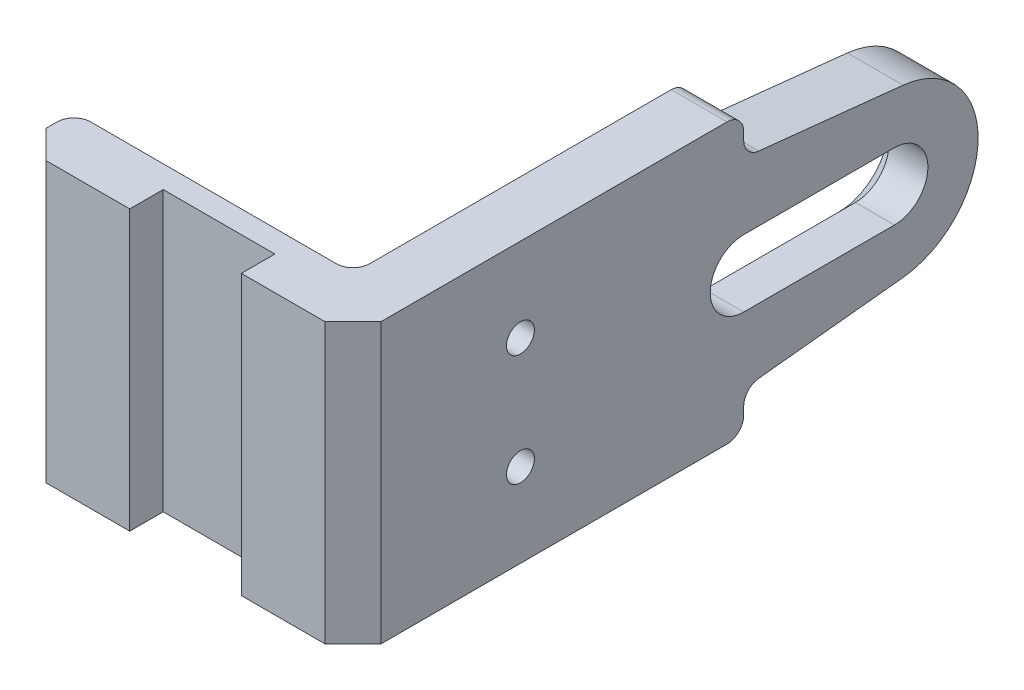
SolidWorks part; units mm, degrees
material "2014-T6"
ref_plane "Front Plane" through (0, 0, 0) normal (0, 0, 1) x (1, 0, 0)
ref_plane "Top Plane" through (0, 0, 0) normal (0, 1, 0) x (1, 0, 0)
ref_plane "Right Plane" through (0, 0, 0) normal (1, 0, 0) x (0, 0, -1)
sketch "Sketch1" plane through (0, 0, 0) normal (0, 1, 0) x (1, 0, 0)
  line L1 (0, 0) -> (-30, 0)
  line L2 (0, 0) -> (0, 10)
  line L3 (-5, 5) -> (-30, 5)
  line L4 (-30, 0) -> (-30, 5)
  line L5 (0, 0) -> (-5, 0)
  line L6 (0, 0) -> (0, 56)
  line L7 (0, 56) -> (-5, 56)
  line L8 (-5, 5) -> (-5, 56)
  dimension "D1" = 30
  dimension "D2" = 5
  dimension "D3" = 5
  dimension "D4" = 56
extrude "Boss-Extrude1" add sketch "Sketch1" along normal blind 25 contours L6 L7 L8 L3 L4 L1
sketch "Sketch2" plane through (0, 0, 0) normal (1, 0, 0) x (0, 0, -1)
  line L0 (0, 25) -> (56, 25) construction
  line L1 (35, 25) -> (56, 25)
  line L2 (35, 25) -> (35, 21.4602)
  line L3 (35, 21.4602) -> (56, 19.253)
  line L4 (56, 25) -> (56, 19.253)
  line L5 (56, 25) -> (56, 0) construction
  line L6 (0, 0) -> (56, 0) construction
  line L7 (35, 3.5398) -> (56, 5.747)
  line L8 (35, 3.5398) -> (35, 0)
  line L9 (35, 0) -> (56, 0)
  line L10 (56, 5.747) -> (56, 0)
  line L11 (0, 25) -> (0, 0) construction
  line L12 (0, 12.5) -> (97, 12.5) construction
  line L13 (56, 19.253) -> (56, 5.747)
  circle A0 centre (48.5, 12.5) radius 7.5
  dimension "D2" = 7.5
  dimension "D1" = 35
  dimension "D3" = 96
  dimension "D4" = 96
extrude "Cut-Extrude1" cut sketch "Sketch2" against normal blind 25 contours L4 L1 L2 L3 | A0 L13 L3 | A0 L7 L13 | L10 L7 L8 L9 region at (0, 22.6346, -46.3318) region at (0, 17.9221, -54.5219) region at (0, 7.0779, -54.5219) region at (0, 2.3654, -46.3318)
sketch "Sketch3" plane through (0, 0, 0) normal (1, 0, 0) x (0, 0, -1)
  line L0 (35, 12.5) -> (48.5, 12.5) construction
  line L1 (35, 15.5) -> (48.5, 15.5)
  line L2 (35, 9.5) -> (48.5, 9.5)
  line L3 (0, 12.5) -> (23.8442, 12.5) construction
  line L4 (0, 25) -> (0, 0) construction
  arc A0 (35, 15.5) -> (35, 9.5) centre (35, 12.5) ccw
  arc A1 (48.5, 9.5) -> (48.5, 15.5) centre (48.5, 12.5) ccw
  arc A2 (49.284, 5.0411) -> (49.284, 19.9589) centre (48.5, 12.5) ccw construction
  point P2 (41.75, 12.5)
  dimension "D1" = 3
  dimension "D2" = 35
  dimension "D3" = 48.5
extrude "Cut-Extrude2" cut sketch "Sketch3" against normal blind 25 contours L2 A1 L1 A0
fillet "Fillet1" radius 1.5 4 edges at (-2.5, 21.4602, -35) (-2.5, 3.5398, -35) (-2.5, 0, -35) (-2.5, 25, -35)
sketch "Sketch5" plane through (0, 0, 0) normal (1, 0, 0) x (0, 0, -1)
  line L0 (0, 0) -> (5, 0) construction
  line L1 (5, 25) -> (33.5, 25) construction
  circle A0 centre (15, 17.5) radius 3
  circle A1 centre (15, 7.5) radius 3
  circle A2 centre (15, 17.5) radius 1.25
  circle A3 centre (15, 7.5) radius 1.25
  dimension "D2" = 6
  dimension "D3" = 6
  dimension "D7" = 2.5
  dimension "D8" = 2.5
  dimension "D1" = 10
  dimension "D4" = 15
  dimension "D5" = 7.5
  dimension "D6" = 7.5
extrude "Cut-Extrude4" cut sketch "Sketch5" against normal blind 25 contours A2 | A3
extrude "Cut-Extrude5" cut sketch "Sketch5<4>" against normal blind 2.5 from offset 2.5 offset against normal yes
sketch "Sketch5<4>" plane through (0, 0, 0) normal (1, 0, 0) x (0, 0, -1) same geometry as "Sketch5"
sketch "Sketch7" plane through (0, 25, 0) normal (0, 1, 0) x (1, 0, 0)
  line L0 (0, 0) -> (-30, 0) construction
  line L1 (-20, 3) -> (-10, 3)
  line L2 (-20, 3) -> (-20, 0)
  line L3 (-20, 0) -> (-10, 0)
  line L4 (-10, 3) -> (-10, 0)
  line L5 (-30, 0) -> (-30, 5) construction
  dimension "D1" = 10
  dimension "D2" = 10
  dimension "D3" = 3
extrude "Cut-Extrude6" cut sketch "Sketch7" against normal through all contours L4 L3 L2 L1
chamfer "Chamfer1" distance 2.5 angle 45 2 edges at (0, 12.5, 0) (-30, 12.5, 0)
fillet "Fillet2" radius 1.5 2 edges at (-30, 12.5, -5) (-5, 12.5, -5)
chamfer "Chamfer2" distance 1.5 angle 45 4 edges at (-5, 9.5, -41.75) (-5, 12.5, -51.5) (-5, 12.5, -32) (-5, 15.5, -41.75)
